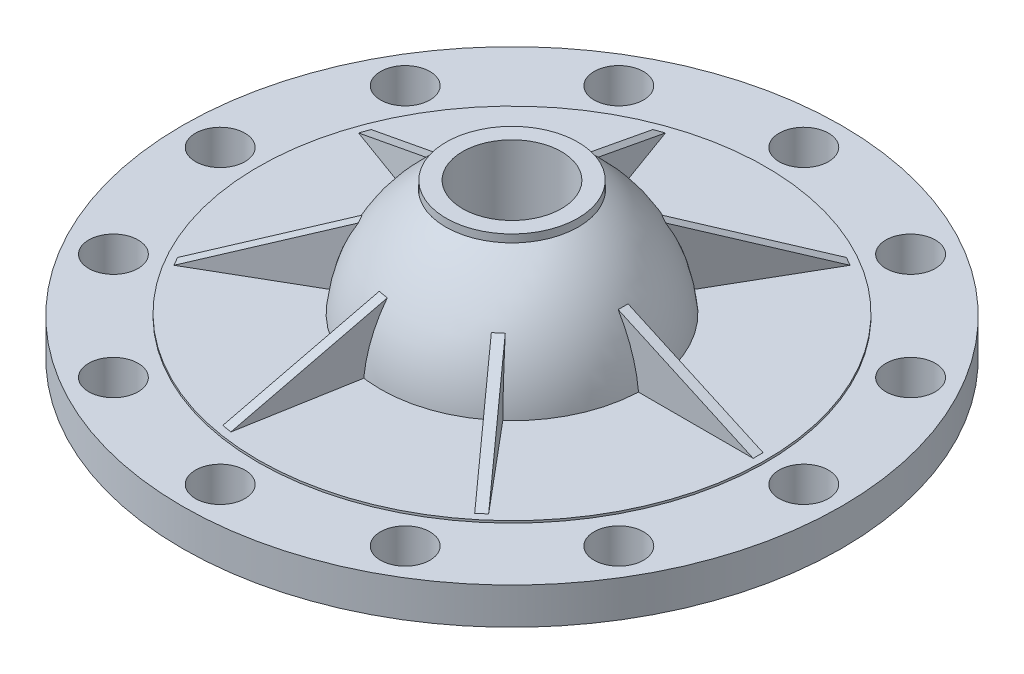
SolidWorks part; units mm, degrees
ref_plane "Front Plane" through (0, 0, 0) normal (0, 0, 1) x (1, 0, 0)
ref_plane "Top Plane" through (0, 0, 0) normal (0, 1, 0) x (1, 0, 0)
ref_plane "Right Plane" through (0, 0, 0) normal (1, 0, 0) x (0, 0, -1)
ref_axis "Axis1" through (0, 42.591, 0) along (0, -1, 0)
sketch "Sketch3" plane through (0, 0, 0) normal (0, 0, 1) x (1, 0, 0)
  line L0 (0, 0) -> (-40.047, 0)
  line L1 (0, 0) -> (0, 45.7409)
  line L2 (0, 42.591) -> (0, -42.6238) construction
  arc A0 (-40.047, 0) -> (0, 45.7409) centre (4.1, 1.7499) cw
  point P5 (0, 0)
  point P6 (0, 45.7409)
sketch "Sketch4" plane through (0, 0, 0) normal (0, 0, 1) x (1, 0, 0)
revolve "Revolve1" add sketch "Sketch3" angle 360 about L1
ref_plane "Plane1" through (0, 40.2174, 0) normal (0, 1, 0) x (1, 0, 0)
sketch "Sketch6" plane through (0, 40.2174, 0) normal (0, 1, 0) x (1, 0, 0)
  circle A0 centre (0, 0) radius 20.0951
extrude "Cut-Extrude2" cut sketch "Sketch6" along normal blind 17 and the other way blind 59
sketch "Sketch7" plane through (0, 0, 0) normal (0, 1, 0) x (1, 0, 0)
  circle A0 centre (0, 0) radius 100
  circle A1 centre (0, 0) radius 39.1422
move or copy body "Body-Move/Copy2" bodies to move or copy 104 copy yes number of copies 1 translate (0, -37.8634, 0) parameters "D1"=0, "D2"=37.8634, "D3"=0
move or copy body "Body-Move/Copy4" bodies to move or copy 106 copy no rotation origin (0, -18.5045, 0) rotation axis (0, 0, 1) rotation angle 180
move or copy body "Body-Move/Copy5" bodies to move or copy 108 copy no translate (0, -0.887, 0) parameters "D1"=0, "D2"=0.887, "D3"=0
extrude "Boss-Extrude1" add sketch "Sketch7" along normal blind 11.0976 separate body
move or copy body "Body-Move/Copy6" bodies to move or copy 110 copy no translate (0, -5.7489, 0) parameters "D1"=0, "D2"=5.7489, "D3"=0
sketch "Sketch8" plane through (0, 0, 0) normal (0, 1, 0) x (1, 0, 0)
  circle A0 centre (0, 0) radius 77
extrude "Boss-Extrude2" add sketch "Sketch8" along normal blind 6
sketch "Sketch16" plane through (0, 0, 0) normal (0, 0, 1) x (1, 0, 0)
  line L0 (33.7083, 24.6094) -> (74.6576, 6)
  line L1 (77, 6) -> (-77, 6) construction
  line L2 (74.6576, 6) -> (39.8768, 6)
  arc A0 (39.8768, 6) -> (20.0951, 38.7176) centre (-4.1, 1.7499) ccw construction
  arc A1 (39.8768, 6) -> (33.7083, 24.6094) centre (-4.1, 1.7499) ccw
extrude "Boss-Extrude13" add sketch "Sketch16" along normal mid plane 3 separate body
pattern_circular "CirPattern5" count 7 every 50 about axis through (0, 42.591, 0) along (0, -1, 0) of bodies 124
sketch "Sketch17" plane through (0, 0, 0) normal (0, 1, 0) x (1, 0, 0)
  line L0 (0, 100) -> (0, 0) construction
  line L1 (0, 0) -> (0, -100) construction
  line L2 (-100, 0) -> (0, 0) construction
  line L3 (0, 0) -> (100, 0) construction
  circle A0 centre (0, 0) radius 100 construction
  circle A1 centre (0, 88.5) radius 7.5
  circle A2 centre (44.25, 76.6432) radius 7.5
  circle A3 centre (76.6432, 44.25) radius 7.5
  circle A4 centre (88.5, 0) radius 7.5
  circle A5 centre (76.6432, -44.25) radius 7.5
  circle A6 centre (44.25, -76.6432) radius 7.5
  circle A7 centre (0, -88.5) radius 7.5
  circle A8 centre (-44.25, -76.6432) radius 7.5
  circle A9 centre (-76.6432, -44.25) radius 7.5
  circle A10 centre (-88.5, 0) radius 7.5
  circle A11 centre (-76.6432, 44.25) radius 7.5
  circle A12 centre (-44.25, 76.6432) radius 7.5
  point P35 (0, 0)
  dimension "D1" = 15
  dimension "D2" = 12
extrude "Cut-Extrude5" cut sketch "Sketch17" against normal through all both and the other way through all
sketch "Sketch18" plane through (0, 6, 0) normal (0, 1, 0) x (1, 0, 0)
  circle A0 centre (0, 0) radius 15
extrude "Extrude-Thin1" add sketch "Sketch18" along normal mid plane 70 thin thin type one direction wall 5
